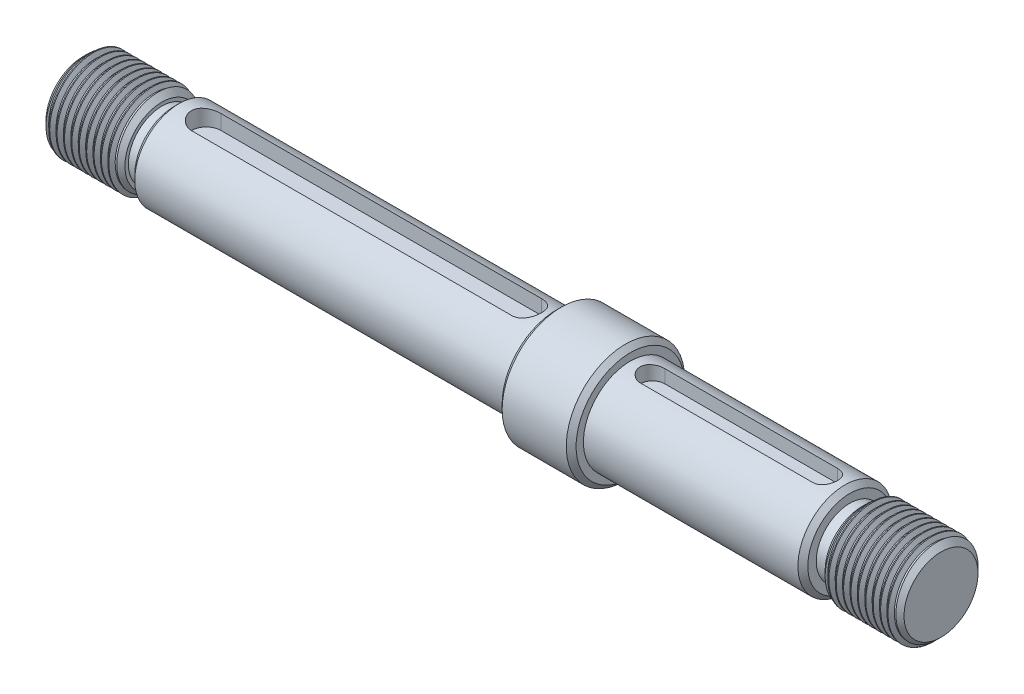
SolidWorks part; units mm, degrees
material "1.0503 (C45)"
ref_plane "前视基准面" through (0, 0, 0) normal (0, 0, 1) x (1, 0, 0)
ref_plane "上视基准面" through (0, 0, 0) normal (0, 1, 0) x (1, 0, 0)
ref_plane "右视基准面" through (0, 0, 0) normal (1, 0, 0) x (0, 0, -1)
sketch "轴轴向刨面" plane through (0, 0, 0) normal (0, 0, 1) x (1, 0, 0)
  line L0 (0, 0) -> (0, 9)
  line L3 (18.5, 9) -> (96, 9)
  line L4 (96, 9) -> (96, 12)
  line L5 (96, 12) -> (111, 12)
  line L6 (111, 12) -> (111, 9.52)
  line L7 (111, 9.52) -> (155.5, 9.52)
  line L8 (174, 9) -> (174, 0)
  line L9 (174, 0) -> (0, 0)
  line L10 (158, 9) -> (174, 9)
  line L12 (18.5, 6.8) -> (16, 6.8)
  line L13 (16, 6.8) -> (16, 9)
  line L14 (0, 9) -> (16, 9)
  line L16 (155.5, 9.52) -> (155.5, 6.8)
  line L17 (155.5, 6.8) -> (158, 6.8)
  line L18 (158, 6.8) -> (158, 9)
  line L19 (18.5, 9) -> (18.5, 6.8)
  dimension "D1" = 44.5
  dimension "D2" = 9
  dimension "D3" = 77.5
  dimension "D4" = 15
  dimension "D5" = 2.5
  dimension "D7" = 2.2
  dimension "D8" = 9.52
  dimension "轴肩半径" = 24
  dimension "大端螺纹长度" = 16
revolve "旋转轴" add sketch "轴轴向刨面" angle 360 about L9
ref_plane "9mm键槽面" through (0, 9, 0) normal (0, 1, 0) x (1, 0, 0)
sketch "草图24" plane through (0, 9, 0) normal (0, 1, 0) x (1, 0, 0)
  line L0 (25, 0) -> (90, 0) construction
  line L3 (25, 3) -> (90, 3)
  line L4 (25, -3) -> (90, -3)
  line L5 (18.5, 6.8) -> (18.5, -6.8) construction
  line L6 (96, 12) -> (96, -12) construction
  arc A2 (25, 3) -> (25, -3) centre (25, 0) ccw
  arc A3 (90, -3) -> (90, 3) centre (90, 0) ccw
  point P2 (57.5, 0)
  point P11 (22, 0)
  point P12 (93, 0)
  dimension "D2" = 6
  dimension "D1" = 3.5
  dimension "D3" = 3
  dimension "D4" = 71
extrude "切除-拉伸11" cut sketch "草图24" against normal blind 3.5
ref_plane "9.52mm键槽面" through (0, 9.52, 0) normal (0, 1, 0) x (1, 0, 0)
sketch "草图25" plane through (0, 9.52, 0) normal (0, 1, 0) x (1, 0, 0)
  line L0 (115.5, 0) -> (150.5, 0) construction
  line L1 (111, 0) -> (155.5, 0) construction
  line L2 (115.5, 2.5) -> (150.5, 2.5)
  line L3 (115.5, -2.5) -> (150.5, -2.5)
  line L5 (155.5, -9.52) -> (155.5, 9.52) construction
  line L6 (111, -9.52) -> (111, 9.52) construction
  arc A0 (115.5, 2.5) -> (115.5, -2.5) centre (115.5, 0) ccw
  arc A1 (150.5, -2.5) -> (150.5, 2.5) centre (150.5, 0) ccw
  point P5 (133, 0)
  point P14 (153, 0)
  point P15 (113, 0)
  dimension "D2" = 2
  dimension "D1" = 5
  dimension "D3" = 2.5
  dimension "D4" = 40
extrude "切除-拉伸12" cut sketch "草图25" against normal blind 3
sketch "草图30" plane through (0, 0, 0) normal (-1, 0, 0) x (0, 0, 1)
  circle A0 centre (0, 0) radius 9 construction
  circle A1 centre (0, 0) radius 9
chamfer "倒角1" distance 1.5 angle 45 4 edges at (174, 0, -9) (158, 0, -9) (16, 0, -9) (0, 0, -9)
chamfer "倒角2" distance 1 angle 45 4 edges at (18.5, 0, -9) (96, 0, -12) (111, 0, -12) (155.5, 0, -9.52)
thread "螺纹线1" pitch 1.5 method cut profile "螺纹线轮廓1" start angle 0, offset 1.5, length 16, pitch 1.5, diameter 18
ref_plane "基准面1" through (0, 0, -9) normal (0, -1, 0) x (0, 0, -1)
sketch "螺纹线轮廓1" plane through (0, 0, -9) normal (0, -1, 0) x (0, 0, -1)
  line L0 (0, 0) -> (0, 1.5) construction
  line L11 (0, 0) -> (0, 1.3125)
  line L12 (0, 1.3125) -> (-0.8119, 0.8437)
  line L13 (-0.8119, 0.8437) -> (-0.8119, 0.4687)
  line L15 (-0.8119, 0.4687) -> (0, 0)
  line L17 (-0.8119, 0.6562) -> (0, 0.6562) construction
  point P2 (0, 0)
  dimension "Pitch" = 1.5
  dimension "Profile_Angle" = 60
  dimension "Profile_Land" = 0.375
  dimension "Profile_Height" = 0.8119
thread "螺纹线2" pitch 1.5 method cut profile "螺纹线轮廓2" start angle 0, offset 1.5, length 16, pitch 1.5, diameter 18
ref_plane "基准面2" through (158, 0, -9) normal (0, -1, 0) x (0, 0, -1)
sketch "螺纹线轮廓2" plane through (158, 0, -9) normal (0, -1, 0) x (0, 0, -1)
  line L0 (0, 0) -> (0, 1.5) construction
  line L11 (0, 0) -> (0, 1.3125)
  line L12 (0, 1.3125) -> (-0.8119, 0.8437)
  line L13 (-0.8119, 0.8437) -> (-0.8119, 0.4687)
  line L15 (-0.8119, 0.4687) -> (0, 0)
  line L17 (-0.8119, 0.6562) -> (0, 0.6562) construction
  point P2 (0, 0)
  dimension "Pitch" = 1.5
  dimension "Profile_Angle" = 60
  dimension "Profile_Land" = 0.375
  dimension "Profile_Height" = 0.8119
